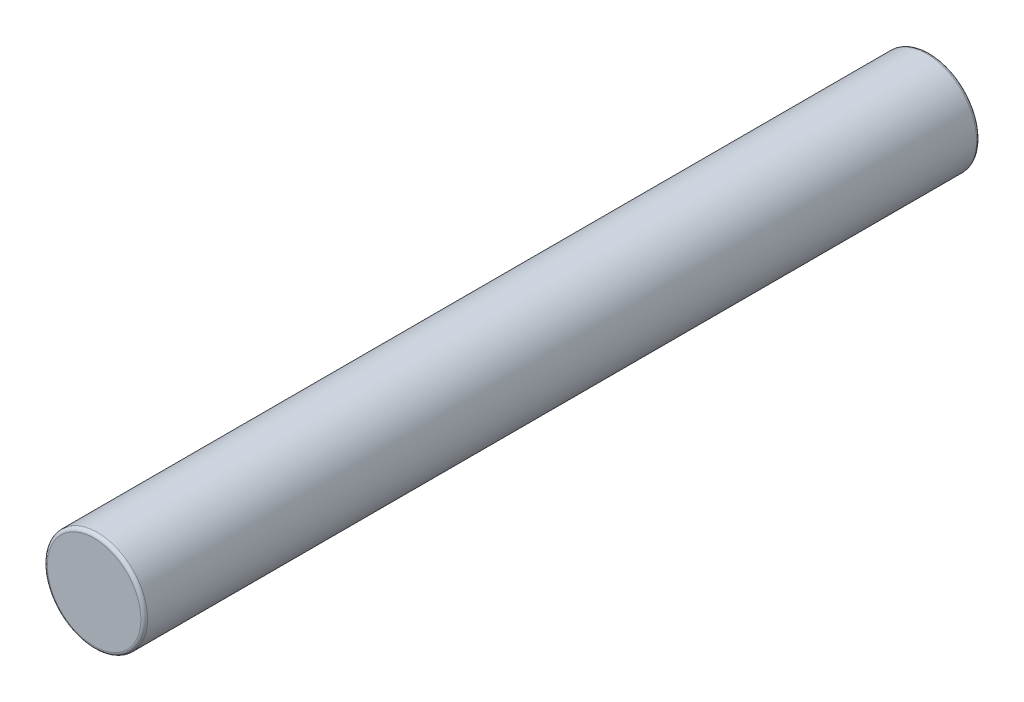
SolidWorks part; units mm, degrees
ref_plane "Front Plane" through (0, 0, 0) normal (0, 0, 1) x (1, 0, 0)
ref_plane "Top Plane" through (0, 0, 0) normal (0, 1, 0) x (1, 0, 0)
ref_plane "Right Plane" through (0, 0, 0) normal (1, 0, 0) x (0, 0, -1)
sketch "Sketch2" plane through (0, 0, 0) normal (0, 0, 1) x (1, 0, 0)
  circle A0 centre (0, 0) radius 3
  dimension "D1" = 6
extrude "Boss-Extrude1" add sketch "Sketch2" along normal blind 50
fillet "Fillet1" radius 0.2 2 edges at (3, 0, 0) (3, 0, 50)
